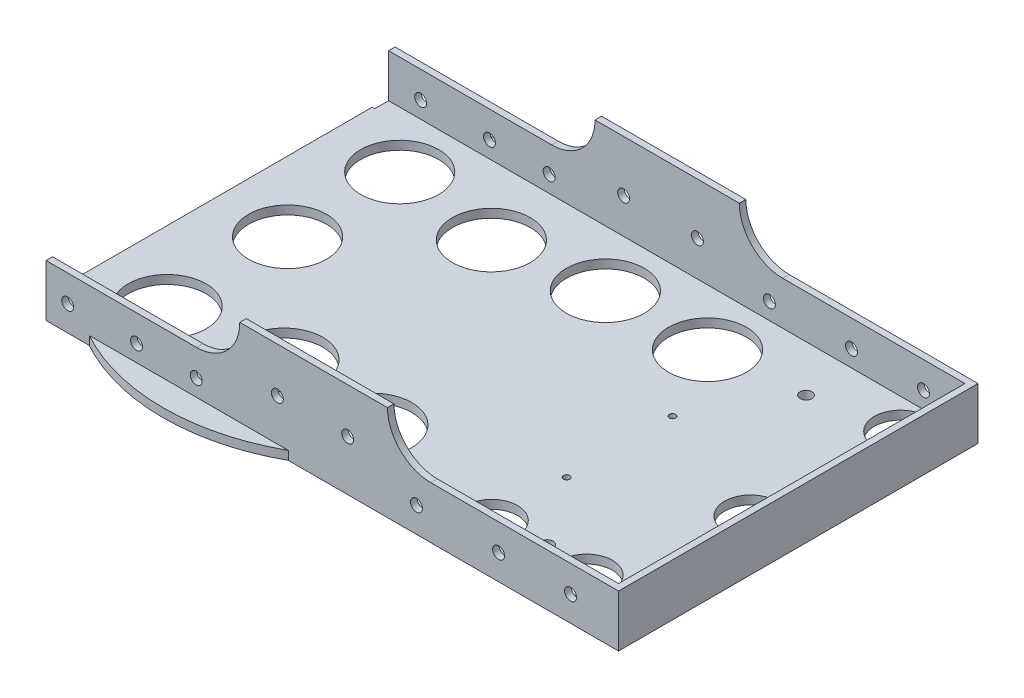
SolidWorks part; units mm, degrees
ref_plane "Front Plane" through (0, 0, 0) normal (0, 0, 1) x (1, 0, 0)
ref_plane "Top Plane" through (0, 0, 0) normal (0, 1, 0) x (1, 0, 0)
ref_plane "Right Plane" through (0, 0, 0) normal (1, 0, 0) x (0, 0, -1)
sketch "Sketch1" plane through (0, 0, 0) normal (0, 1, 0) x (1, 0, 0)
  line L1 (0, 0) -> (278.0499, 0)
  line L2 (0, 0) -> (0, 166.0007)
  line L3 (0, 166.0007) -> (278.0499, 166.0007)
  line L4 (278.0499, 0) -> (278.0499, 166.0007)
extrude "Boss-Extrude1" add sketch "Sketch1" along normal blind 24
sketch "Sketch2" plane through (0, 0, 0) normal (0, -1, 0) x (-1, 0, 0)
  line L1 (-7.6506, 156.6405) -> (14.2402, 156.6405)
  line L2 (-7.6506, 156.6405) -> (-7.6506, 11.5417)
  line L3 (-7.6506, 11.5417) -> (14.2402, 11.5417)
  line L4 (14.2402, 156.6405) -> (14.2402, 11.5417)
extrude "Cut-Extrude1" cut sketch "Sketch2" against normal through all
sketch "Sketch3" plane through (0, 24, 0) normal (0, 1, 0) x (1, 0, 0)
  line L0 (226.9955, 0) -> (226.9955, 3) construction
  line L1 (0, 0) -> (278.0499, 0) construction
  line L2 (278.0499, 166.0007) -> (278.0499, 163.0007) construction
  line L3 (278.0499, 0) -> (278.0499, 166.0007) construction
  line L4 (0, 155.7398) -> (3, 155.7398) construction
  line L5 (0, 166.0007) -> (0, 156.6405) construction
  line L6 (278.0499, 22.4963) -> (275.0499, 22.4963) construction
  line L7 (275.0499, 163.0007) -> (275.0499, 3)
  line L8 (275.0499, 3) -> (3, 3)
  line L9 (3, 3) -> (3, 163.0007)
  line L10 (3, 163.0007) -> (275.0499, 163.0007)
extrude "Cut-Extrude2" cut sketch "Sketch3" against normal blind 20
sketch "Sketch4" plane through (0, 24, 0) normal (0, 1, 0) x (1, 0, 0)
  line L0 (0, 0) -> (278.0499, 0) construction
  line L1 (171.3453, 0) -> (103.1403, 0)
  line L2 (171.3453, 0) -> (171.3453, 3)
  line L3 (171.3453, 3) -> (103.1403, 3)
  line L4 (103.1403, 0) -> (103.1403, 3)
  line L5 (3, 3) -> (275.0499, 3) construction
extrude "Boss-Extrude2" add sketch "Sketch4" along normal blind 20
fillet "Fillet4" radius 20 1 edges at (103.1403, 24, -1.5) type face fillet first side face at (103.1403, 34, -1.5) second side face at (35.3801, 24, -4.8472)
fillet "Fillet5" radius 20 1 edges at (171.3453, 24, -1.5) type face fillet first side face at (145.489, 24, -97.7284) second side face at (171.3453, 34, -1.5)
sketch "Sketch5" plane through (0, 24, 0) normal (0, 1, 0) x (1, 0, 0)
  line L0 (278.0499, 166.0007) -> (0, 166.0007) construction
  line L1 (104.1867, 166.0007) -> (170.8443, 166.0007)
  line L2 (104.1867, 166.0007) -> (104.1867, 163.0007)
  line L3 (104.1867, 163.0007) -> (170.8443, 163.0007)
  line L4 (170.8443, 166.0007) -> (170.8443, 163.0007)
  line L5 (275.0499, 163.0007) -> (3, 163.0007) construction
extrude "Boss-Extrude3" add sketch "Sketch5" along normal blind 20
fillet "Fillet6" radius 20 1 edges at (104.1867, 24, -164.5007) type face fillet first side face at (104.1867, 34, -164.5007) second side face at (35.7289, 24, -161.8806)
fillet "Fillet7" radius 20 1 edges at (170.8443, 24, -164.5007) type face fillet first side face at (170.8443, 34, -164.5007) second side face at (228.8223, 24, -83.0003)
sketch "Sketch6" plane through (0, 0, -163.0007) normal (0, 0, 1) x (1, 0, 0)
  circle A0 centre (151.5064, 20.306) radius 2.75
  circle A1 centre (117.3926, 20.306) radius 2.75
extrude "HolesForBolts1" cut sketch "Sketch6" against normal through all
sketch "Sketch7" plane through (0, 0, -166.0007) normal (0, 0, -1) x (-1, 0, 0)
  circle A0 centre (-23.6542, 11.6758) radius 2.75
  circle A1 centre (-55.4415, 11.6758) radius 2.75
  circle A2 centre (-83.0044, 11.6758) radius 2.75
  circle A3 centre (-184.7276, 11.6758) radius 2.75
  circle A4 centre (-222.6455, 11.6758) radius 2.75
  circle A5 centre (-255.8817, 11.6758) radius 2.75
extrude "Cut-Extrude4" cut sketch "Sketch7" against normal through all
sketch "Sketch8" plane through (0, 0, -3) normal (0, 0, -1) x (-1, 0, 0)
  circle A0 centre (-120.4871, 23.2804) radius 2.75
  circle A1 centre (-152.9663, 23.2804) radius 2.75
extrude "Cut-Extrude5" cut sketch "Sketch8" against normal blind 20
ref_plane "Plane1" through (0, 0, -11.5417) normal (0, 0, 1) x (1, 0, 0)
sketch "Sketch11" plane through (0, 0, 0) normal (0, -1, 0) x (1, 0, 0)
  line L0 (7.6506, -11.5417) -> (0, -11.5417) construction
  line L1 (0, 0) -> (13.6461, 0)
  line L2 (0, 0) -> (0, -11.5417)
  line L3 (0, -11.5417) -> (13.6461, -11.5417)
  line L4 (13.6461, 0) -> (13.6461, -11.5417)
extrude "Cut-Extrude6" cut sketch "Sketch11" against normal through all
sketch "Sketch12" plane through (0, 0, 0) normal (0, -1, 0) x (1, 0, 0)
  line L0 (0, -156.6405) -> (7.6506, -156.6405) construction
  line L1 (0, -166.0007) -> (8.8441, -166.0007)
  line L2 (0, -166.0007) -> (0, -156.6405)
  line L3 (0, -156.6405) -> (8.8441, -156.6405)
  line L4 (8.8441, -166.0007) -> (8.8441, -156.6405)
extrude "Cut-Extrude7" cut sketch "Sketch12" against normal through all
sketch "HolesInLidForPiCover" plane through (0, 0, 0) normal (0, -1, 0) x (1, 0, 0)
  circle A0 centre (223.0138, -141.6086) radius 2.75
  circle A1 centre (223.0138, -22.1297) radius 2.75
extrude "Cut-Extrude8" cut sketch "HolesInLidForPiCover" against normal up to surface (4 mm away) up to face at (76.2977, 4, -83.5457)
ref_point "RasPiBoltPoint1"
ref_point "RasPiBoltPoint2"
ref_point "RasPiBoltPoint3"
ref_point "RasPiBoltPoint4"
sketch "LidHolesForPi" plane through (0, 0, 0) normal (0, -1, 0) x (1, 0, 0)
  circle A0 centre (200.5621, -102.3707) radius 1.455
  circle A1 centre (200.5621, -53.5029) radius 1.455
  circle A2 centre (258.5449, -53.5029) radius 1.455
  circle A3 centre (258.5449, -102.3707) radius 1.455
extrude "Cut-Extrude9" cut sketch "LidHolesForPi" against normal up to surface (4 mm away) up to face at (223.0138, 4, -24.8797)
ref_point "LidHoleForCoverLocation1"
ref_point "LidHoleForCoverLocation2"
sketch "Sketch14" plane through (0, 0, 0) normal (0, -1, 0) x (1, 0, 0)
  circle A0 centre (264.7636, -18.9201) radius 2.75
  circle A1 centre (181.6168, -18.9187) radius 2.75
extrude "Cut-Extrude10" cut sketch "Sketch14" against normal up to surface (4 mm away) up to face at (258.5449, 4, -54.9579)
sketch "Sketch15" plane through (0, 0, 1.7414) normal (0, -1, 0) x (1, 0, 0)
  circle A0 centre (79.5908, -84.8811) radius 95
extrude "Boss-Extrude4" add sketch "Sketch15" against normal up to surface (4 mm away) up to face at (181.6168, 4, -21.6687)
sketch "Sketch16" plane through (0, 0, 0) normal (0, -1, 0) x (1, 0, 0)
  line L1 (7.6506, -21.0945) -> (-30.4108, -21.0945)
  line L2 (7.6506, -21.0945) -> (7.6506, -147.5505)
  line L3 (7.6506, -147.5505) -> (-30.4108, -147.5505)
  line L4 (-30.4108, -21.0945) -> (-30.4108, -147.5505)
extrude "Cut-Extrude11" cut sketch "Sketch16" against normal up to surface (4 mm away) up to face at (60.2623, 4, -83.4645)
sketch "Sketch17" plane through (0, 0, 0) normal (0, -1, 0) x (1, 0, 0)
  circle A0 centre (259.219, -148.9495) radius 11.9637
  circle A1 centre (134.9145, -137.0513) radius 18
  circle A2 centre (134.9145, -29.6569) radius 18
  circle A3 centre (88.3199, -130.9946) radius 18
  circle A4 centre (88.3199, -35.2146) radius 18
  circle A5 centre (182.0825, -137.0513) radius 18
  circle A6 centre (39.9405, -137.0513) radius 18
  circle A7 centre (39.9405, -29.6569) radius 18
  circle A8 centre (39.9405, -85.2631) radius 18
  circle A9 centre (244.3074, -18.9186) radius 11.9637
  circle A10 centre (200.5499, -18.9186) radius 11.9637
  circle A11 centre (258.5499, -80.4439) radius 11.9637
  point P4 (194.5372, -148.9495)
  point P7 (134.9145, -148.9495)
  point P8 (134.9145, -18.9186)
  point P9 (134.9145, -148.9495)
  point P10 (134.9145, -137.6238)
  point P11 (134.9145, -35.7204)
  point P12 (134.9145, -140.3583)
  point P13 (134.9145, -137.0513)
  point P15 (134.9145, -29.6569)
  point P19 (88.3199, -137.0513)
  point P20 (0, 0)
  point P21 (182.0825, -137.0513)
  point P22 (88.3199, -29.6569)
  point P27 (39.9405, -137.0513)
  point P30 (39.9405, -29.6569)
  point P33 (39.9405, -85.2631)
  point P36 (244.3074, -18.9186)
  point P39 (200.5499, -18.9186)
  point P42 (258.5499, -80.4439)
  point P43 (0, 0)
  point P44 (88.3199, -35.2146)
  point P45 (88.3199, -130.9946)
extrude "Cut-Extrude12" cut sketch "Sketch17" against normal up to surface (4 mm away) up to face at (76.2977, 4, -83.5457)
